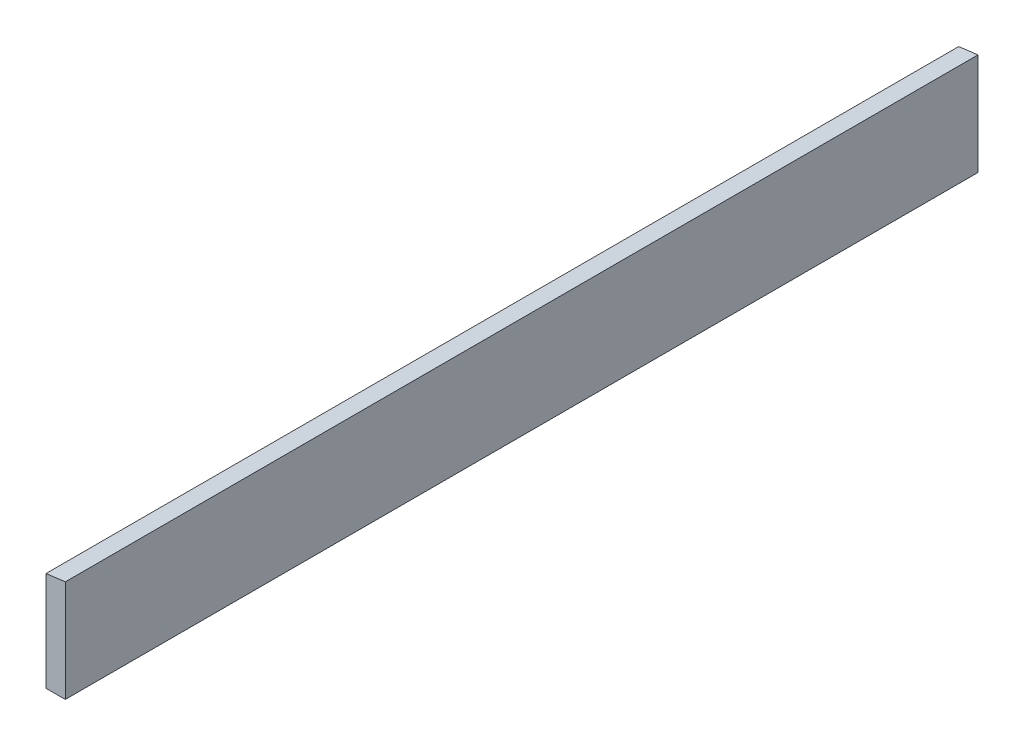
SolidWorks part; units mm, degrees
material "Pine"
ref_plane "Front Plane" through (0, 0, 0) normal (0, 0, 1) x (1, 0, 0)
ref_plane "Top Plane" through (0, 0, 0) normal (0, 1, 0) x (1, 0, 0)
ref_plane "Right Plane" through (0, 0, 0) normal (1, 0, 0) x (0, 0, -1)
sketch "Sketch1" plane through (0, 0, 0) normal (0, 0, 1) x (1, 0, 0)
  line L0 (207.3863, 27.1947) -> (486.7863, 27.1947)
  line L1 (486.7863, 27.1947) -> (486.7863, 179.5947)
  line L2 (486.7863, 179.5947) -> (79.2003, 128.6129)
  line L4 (486.7863, 160.3962) -> (81.5647, 109.7102)
  line L6 (467.7363, 158.0134) -> (251.8363, 131.0081) construction
  line L7 (467.7363, 27.1947) -> (467.7363, 158.0134)
  line L8 (251.8363, 46.2447) -> (467.7363, 46.2447) construction
  line L9 (251.8363, 131.0081) -> (251.8363, 46.2447) construction
  line L10 (467.7363, 46.2447) -> (467.7363, 158.0134) construction
  line L11 (486.7863, 160.3962) -> (484.4219, 179.2989)
  line L12 (486.7863, 27.1947) -> (486.7863, 179.5947) construction
  line L13 (486.7863, 179.5947) -> (232.7863, 147.8238) construction
  line L14 (81.5647, 109.7102) -> (60.2851, 279.8345) construction
  line L15 (232.7863, 147.8238) -> (232.7863, 27.1947) construction
  line L16 (81.5647, 109.7102) -> (79.2003, 128.6129)
  line L17 (484.4219, 179.2989) -> (230.4219, 147.528) construction
  line L18 (226.4363, 127.8311) -> (226.4363, 27.1947)
  line L19 (207.3863, 125.4482) -> (207.3863, 27.1947)
  line L20 (226.4363, 131.0081) -> (226.4363, 27.1947) construction
  line L21 (207.3863, 131.0081) -> (207.3863, 27.1947) construction
  line L22 (616.7284, 349.4357) -> (60.2851, 279.8345) construction
  line L23 (638.0079, 179.3114) -> (616.7284, 349.4357) construction
  line L24 (232.7863, 128.6253) -> (230.4219, 147.528) construction
  line L25 (232.7863, 27.1947) -> (486.7863, 27.1947) construction
  dimension "D1" = 97.13
extrude "Boss-Extrude1" add sketch "Sketch1" along normal blind 901.7 contours L4 L0 region at (216.9493, 76.9195, 0)
